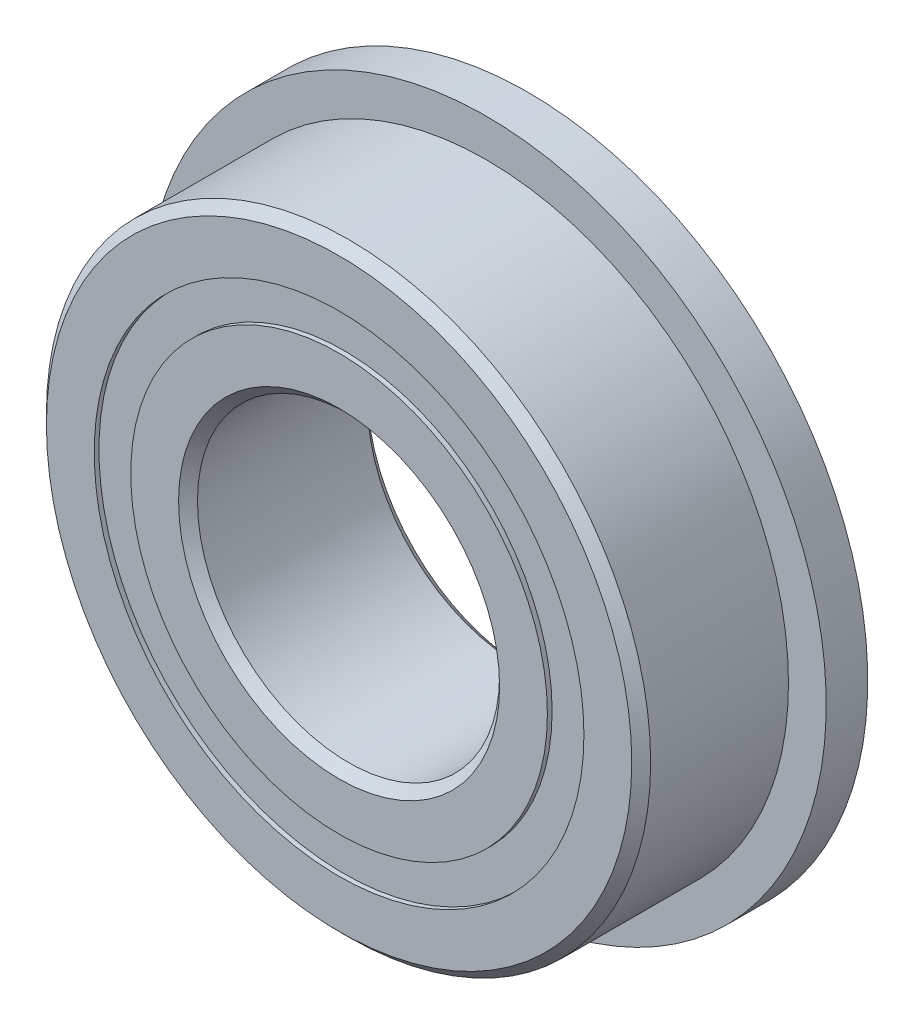
SolidWorks part; units mm, degrees
ref_plane "Front Plane" through (0, 0, 0) normal (0, 0, 1) x (1, 0, 0)
ref_plane "Top Plane" through (0, 0, 0) normal (0, 1, 0) x (1, 0, 0)
ref_plane "Right Plane" through (0, 0, 0) normal (1, 0, 0) x (0, 0, -1)
sketch "Sketch1" plane through (0, 0, 0) normal (1, 0, 0) x (0, 0, -1)
  line L0 (-2.5, 0) -> (2.5, 0) construction
  line L1 (0, 8) -> (0, -8) construction
  line L2 (2.25, 8) -> (-2.25, 8)
  line L3 (-2.25, 8) -> (-2.5, 7.75)
  line L4 (-2.5, 7.75) -> (-2.5, 6.4835)
  line L5 (-2.5, 6.4835) -> (-1.1111, 6.4835)
  line L6 (2.5, 6.4835) -> (1.1111, 6.4835)
  line L7 (2.5, 7.75) -> (2.5, 6.4835)
  line L8 (2.25, 8) -> (2.5, 7.75)
  line L9 (0, 8) -> (0, 6) construction
  line L10 (0, 6) -> (0, 4) construction
  arc A0 (-1.1111, 6.4835) -> (1.1111, 6.4835) centre (0, 6) cw
  point P14 (0, 4)
  dimension "D3" = 2.2222
  dimension "D1" = 45
  dimension "Width" = 5
  dimension "OD" = 16
  dimension "D2" = 0.25
  dimension "Shaft Dia" = 8
  dimension "D4" = 0.4835
revolve "Revolve1" add sketch "Sketch1" angle 360 about L0
sketch "Sketch3" plane through (0, 0, 0) normal (1, 0, 0) x (0, 0, -1)
  line L0 (-2.5, 5.5165) -> (-1.1111, 5.5165)
  line L1 (0, 8) -> (0, -8) construction
  line L2 (-2.5, 7.75) -> (-2.5, 6.4835) construction
  line L3 (-2.5, 5.5165) -> (-2.5, 4.25)
  line L4 (-2.25, 8) -> (-2.5, 7.75) construction
  line L5 (-2.5, 4.25) -> (-2.25, 4)
  line L6 (-2.25, 4) -> (2.25, 4)
  line L7 (2.25, 8) -> (2.25, -8) construction
  line L8 (2.25, 4) -> (2.5, 4.25)
  line L9 (2.5, -7.75) -> (2.5, 7.75) construction
  line L10 (2.5, 4.25) -> (2.5, 5.5165)
  line L11 (2.5, 5.5165) -> (1.1111, 5.5165)
  line L13 (2.25, 8) -> (2.5, 7.75) construction
  arc A0 (1.1111, 6.4835) -> (-1.1111, 6.4835) centre (0, 6) ccw construction
  arc A1 (1.1111, 5.5165) -> (-1.1111, 5.5165) centre (0, 6) cw
revolve "Revolve3" add sketch "Sketch3" angle 360 about L0
sketch "Sketch4" plane through (0, 0, 0) normal (1, 0, 0) x (0, 0, -1)
  line L0 (-1.2118, 6) -> (1.2118, 6)
  arc A2 (-1.2118, 6) -> (1.2118, 6) centre (0, 6) cw
  arc A3 (1.1111, 6.4835) -> (-1.1111, 6.4835) centre (0, 6) ccw construction
revolve "Revolve4" add sketch "Sketch4" angle 360 about L0
ref_axis "Axis1" through (0, 0, -2.5) along (0, 0, 1)
pattern_circular "CirPattern1" count 12 every 30 about axis through (0, 0, -2.5) along (0, 0, 1) of bodies 104
sketch "Sketch5" plane through (0, 0, 0) normal (1, 0, 0) x (0, 0, -1)
  line L0 (-2.5, 6.4835) -> (-1.1111, 6.4835) construction
  line L1 (-2.375, 6.4835) -> (-1.2118, 6.4835)
  line L2 (-2.375, 6.4835) -> (-2.375, 5.5165)
  line L3 (-2.375, 5.5165) -> (-1.2118, 5.5165)
  line L4 (-1.2118, 6.4835) -> (-1.2118, 5.5165)
  line L5 (-2.5, 5.5165) -> (-1.1111, 5.5165) construction
  line L6 (2.5, 6.4835) -> (1.1111, 6.4835) construction
  line L7 (2.375, 6.4835) -> (1.2118, 6.4835)
  line L8 (2.375, 6.4835) -> (2.375, 5.5165)
  line L9 (2.375, 5.5165) -> (1.2118, 5.5165)
  line L10 (1.2118, 6.4835) -> (1.2118, 5.5165)
  line L11 (2.5, 5.5165) -> (1.1111, 5.5165) construction
  line L12 (-2.25, 8) -> (-2.5, 7.75) construction
  point P18 (-2.375, 7.875)
revolve "Revolve5" add sketch "Sketch5" angle 360 about L0
sketch "Sketch6" plane through (0, 0, 0) normal (1, 0, 0) x (0, 0, -1)
  line L0 (2.5, 0) -> (-2.5, 0) construction
  line L1 (2.5, 6.4835) -> (1.4, 6.4835)
  line L2 (2.5, 6.4835) -> (2.5, 9)
  line L3 (2.5, 9) -> (1.4, 9)
  line L4 (1.4, 6.4835) -> (1.4, 9)
  dimension "Th" = 1.1
  dimension "Flange OD" = 18
revolve "Revolve6" add sketch "Sketch6" angle 360 about L0
equation "\"D2@Sketch1\" = \"Width@Sketch1\"*.05"
equation "\"D3@Sketch1\" = \"Width@Sketch1\"/2.25"
equation "\"D4@Sketch1\" = (((\"OD@Sketch1\"-\"Width@Sketch1\")/2)/3.25)/3.5"
equation "\"D2@CirPattern1\" = 360/\"Balls@CirPattern1\""
